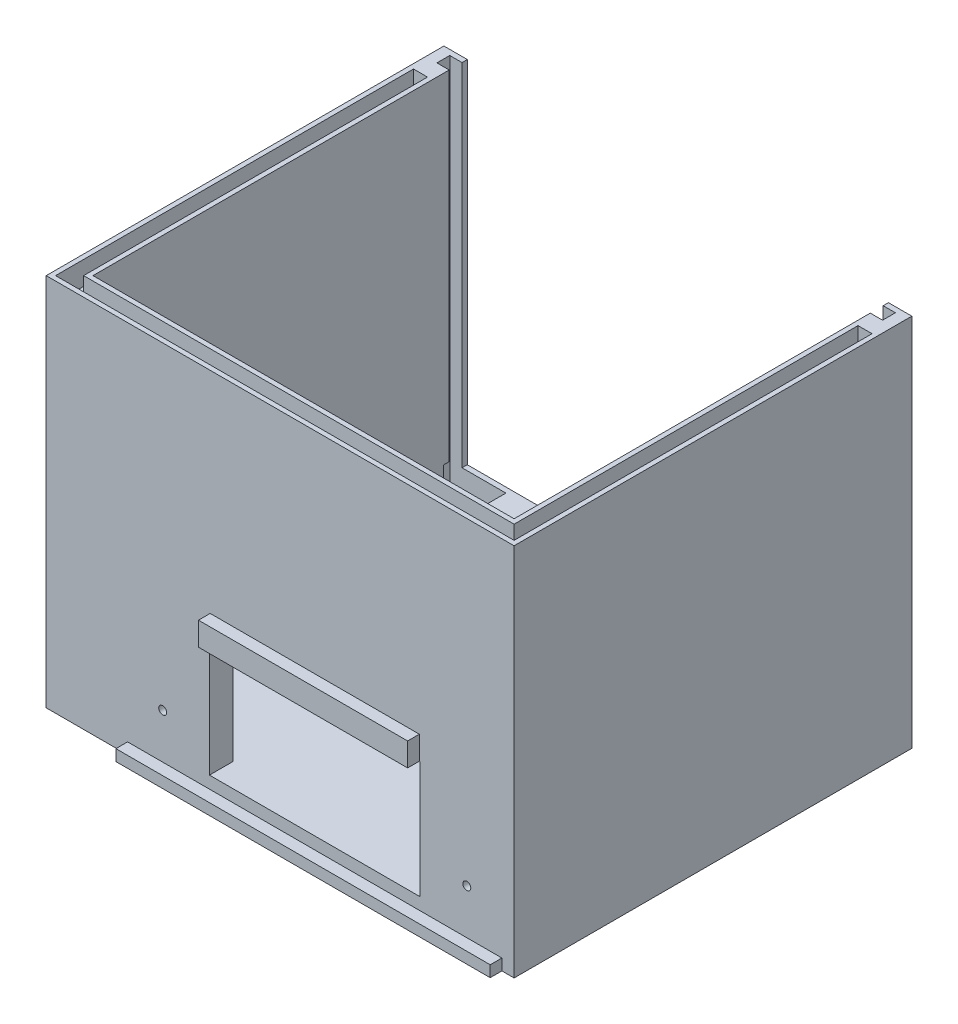
SolidWorks part; units mm, degrees
ref_plane "Front Plane" through (0, 0, 0) normal (0, 0, 1) x (1, 0, 0)
ref_plane "Top Plane" through (0, 0, 0) normal (0, 1, 0) x (1, 0, 0)
ref_plane "Right Plane" through (0, 0, 0) normal (1, 0, 0) x (0, 0, -1)
sketch "Croquis1" plane through (0, 0, 0) normal (0, 1, 0) x (1, 0, 0)
  line L1 (-100, -85) -> (100, -85)
  line L2 (-100, -85) -> (-100, 85)
  line L3 (-100, 85) -> (100, 85)
  line L4 (100, -85) -> (100, 85)
  line L5 (-100, -85) -> (100, 85) construction
  line L6 (-100, 85) -> (100, -85) construction
  point P0 (0, 0)
  dimension "D1" = 200
  dimension "D2" = 170
extrude "Saliente-Extruir1" add sketch "Croquis1" along normal blind 10
sketch "Croquis2" plane through (0, 10, 0) normal (0, 1, 0) x (1, 0, 0)
  line L0 (-100, 85) -> (-100, -85) construction
  line L1 (-100, -85) -> (-90, -85)
  line L2 (-100, -85) -> (-100, 85)
  line L3 (-100, 85) -> (-90, 85)
  line L4 (-90, -85) -> (-90, 85)
  line L5 (-100, -85) -> (-90, 85) construction
  line L6 (-100, 85) -> (-90, -85) construction
  line L7 (0, 0) -> (0, 38.7105) construction
  line L8 (100, 85) -> (90, -85) construction
  line L9 (100, -85) -> (90, 85) construction
  line L10 (90, -85) -> (90, 85)
  line L11 (100, 85) -> (90, 85)
  line L12 (100, -85) -> (100, 85)
  line L13 (100, -85) -> (90, -85)
  line L14 (-90, 85) -> (90, 85)
  line L15 (-90, 75) -> (90, 75)
  line L16 (-90, -75) -> (-30.21, -75)
  line L17 (-30.21, -75) -> (-30.21, -85)
  line L18 (-100, -85) -> (100, -85) construction
  line L19 (-30.21, -85) -> (-90, -85)
  line L20 (59.79, -85) -> (59.79, -75)
  line L21 (59.79, -75) -> (90, -75)
  line L22 (59.79, -85) -> (90, -85)
  point P0 (-95, 0)
  point P14 (95, 0)
  line M14 (100, -85) -> (100, 85)
  line M15 (100, 85) -> (-100, 85)
  line M16 (-100, 85) -> (-100, -85)
  line M17 (-100, -85) -> (100, -85)
  dimension "D1" = 10
  dimension "D2" = 10
  dimension "D3" = 10
  dimension "D4" = 69.79
  dimension "D5" = 40.21
  dimension "D6" = 10
extrude "Saliente-Extruir2" add sketch "Croquis2" along normal blind 150 contours L4 M17 M15 M16 | L10 M17 M14 M15 | L17 L16 L4 M17 | L21 L20 L10 M17 region at (-95, 10, 0) region at (-60.105, 10, 80) region at (74.895, 10, 80) region at (95, 10, 0)
sketch "Croquis3" plane through (0, 160, 0) normal (0, 1, 0) x (1, 0, 0)
  line L0 (-30.21, -75) -> (59.79, -75)
  line L1 (59.79, -75) -> (59.79, -85)
  line L2 (59.79, -85) -> (-30.21, -85)
  line L3 (-30.21, -85) -> (-30.21, -75)
extrude "Saliente-Extruir3" add sketch "Croquis3" against normal blind 100
sketch "Croquis4" plane through (0, 10, 65) normal (0, 1, 0) x (-1, 0, 0)
  line L1 (95.25, -147.75) -> (84.75, -147.75)
  line L2 (95.25, -147.75) -> (95.25, -142.25)
  line L3 (95.25, -142.25) -> (84.75, -142.25)
  line L4 (84.75, -147.75) -> (84.75, -142.25)
  line L5 (95.25, -147.75) -> (84.75, -142.25) construction
  line L6 (95.25, -142.25) -> (84.75, -147.75) construction
  line L8 (90, -142.25) -> (90, -147.75)
  line L9 (0, -65) -> (0, 148.7254) construction
  line L10 (-95.25, -142.25) -> (-84.75, -147.75) construction
  line L11 (-95.25, -147.75) -> (-84.75, -142.25) construction
  line L12 (-90, -142.25) -> (-90, -147.75)
  line L13 (-84.75, -147.75) -> (-84.75, -142.25)
  line L14 (-95.25, -142.25) -> (-84.75, -142.25)
  line L15 (-95.25, -147.75) -> (-95.25, -142.25)
  line L16 (-95.25, -147.75) -> (-84.75, -147.75)
  line L17 (-90, -150) -> (90, -150) construction
  line L18 (90, 10) -> (90, -150) construction
  point P0 (90, -145)
  point P20 (-90, -145)
  dimension "D1" = 5.5
  dimension "D2" = 5
  dimension "D3" = 10.5
extrude "Cortar-Extruir1" cut sketch "Croquis4" along normal blind 170 contours L2 L3 L1 | L15 L16 L14 region at (-92.625, 10, -80) region at (92.625, 10, -80)
sketch "Croquis7" plane through (0, 0, 85) normal (0, 0, 1) x (1, 0, 0)
  line L0 (-30.21, 60) -> (-30.21, 70)
  line L1 (-30.21, 70) -> (59.79, 70)
  line L2 (59.79, 70) -> (59.79, 60)
  line L3 (-30.21, 60) -> (59.79, 60)
  dimension "D1" = 10
extrude "Saliente-Extruir4" add sketch "Croquis7" along normal blind 5
sketch "Croquis8" plane through (0, 160, 0) normal (0, 1, 0) x (1, 0, 0)
  line L4 (98, 70) -> (98, -83)
  line L5 (98, -83) -> (-98, -83)
  line L6 (-98, -83) -> (-98, 70)
  line L8 (-98, 70) -> (-92, 70)
  line L9 (-92, 70) -> (-92, -77)
  line L10 (-92, -77) -> (92, -77)
  line L11 (92, -77) -> (92, 70)
  line L12 (92, 70) -> (98, 70)
  line L13 (100, -85) -> (100, 85) construction
  line L14 (90, -75) -> (90, 77.25) construction
  line L25 (-100, -85) -> (100, -85) construction
  line L26 (-90, -75) -> (90, -75) construction
  line L33 (-90, -75) -> (-90, 77.25) construction
  line L34 (-100, 85) -> (-100, -85) construction
  line L68 (-90, 85) -> (-100, 85) construction
  line L69 (100, 85) -> (90, 85) construction
  dimension "D1" = 2
  dimension "D2" = 2
  dimension "D3" = 2
  dimension "D4" = 2
  dimension "D5" = 2
  dimension "D7" = 15
  dimension "D8" = 15
  dimension "D6" = 2
extrude "Cortar-Extruir3" cut sketch "Croquis8" against normal blind 10 contours L8 region at (95.5135, 160, 6.5)
sketch "Croquis9" plane through (0, 10, 0) normal (0, 1, 0) x (1, 0, 0)
  line L0 (-95.25, 77.25) -> (-95.25, 82.75)
  line L1 (-95.25, 82.75) -> (-71.25, 82.75)
  line L2 (-71.25, 82.75) -> (-71.25, 77.25)
  line L4 (-71.25, 77.25) -> (-71.25, 74.75)
  line L5 (-71.25, 74.75) -> (-95.25, 74.75)
  line L6 (-95.25, 74.75) -> (-95.25, 77.25)
  dimension "D1" = 24
  dimension "D2" = 2.5
  dimension "D3" = 2.5
extrude "Cortar-Extruir4" cut sketch "Croquis9" against normal blind 30
extrude "Cortar-Extruir5" cut sketch "Croquis9<2>" along normal blind 5
sketch "Croquis9<2>" plane through (0, 10, 0) normal (0, 1, 0) x (1, 0, 0) same geometry as "Croquis9"
sketch "Croquis10" plane through (0, 0, 0) normal (0, -1, 0) x (1, 0, 0)
  line L0 (-71.25, -82.75) -> (-95.25, -82.75)
  line L1 (-95.25, -82.75) -> (-95.25, -74.75)
  line L2 (-95.25, -74.75) -> (-71.25, -74.75)
  line L3 (-71.25, -74.75) -> (-71.25, -82.75)
  line L4 (-68.25, -85.25) -> (-98.25, -85.25)
  line L5 (-98.25, -85.25) -> (-98.25, -71.75)
  line L6 (-98.25, -71.75) -> (-68.25, -71.75)
  line L7 (-68.25, -71.75) -> (-68.25, -85.25)
  dimension "D1" = 3
  dimension "D2" = 3
  dimension "D3" = 3
  dimension "D4" = 2.5
extrude "Saliente-Extruir5" add sketch "Croquis10" along normal blind 4.3
sketch "Croquis11" plane through (0, 0, -71.75) normal (0, 0, 1) x (1, 0, 0)
  line L0 (-68.25, -4.3) -> (-68.25, 0) construction
  line L1 (-68.25, 0) -> (-98.25, 0) construction
  circle A0 centre (-77.55, -2.1) radius 1.1
  circle A1 centre (-86.93, -2.1) radius 1.1
  dimension "D1" = 2.2
  dimension "D2" = 2.2
  dimension "D3" = 9.3
  dimension "D4" = 9.38
  dimension "D5" = 2.1
  dimension "D6" = 2.1
extrude "Cortar-Extruir6" cut sketch "Croquis11" against normal blind 14.3
sketch "Croquis12" plane through (0, 0, 0) normal (0, -1, 0) x (1, 0, 0)
  line L0 (-100, -85) -> (-100, 85) construction
  line L1 (0, 0) -> (-59.6706, 0) construction
  line L2 (100, -85) -> (-68.25, -85) construction
  circle A0 centre (-91.5, -55) radius 1.75
  circle A1 centre (18.5, -55) radius 1.75
  circle A2 centre (-91.5, 55) radius 1.75
  circle A3 centre (18.5, 55) radius 1.75
  dimension "D1" = 3.5
  dimension "D4" = 3.5
  dimension "D5" = 30
  dimension "D6" = 30
  dimension "D2" = 8.5
  dimension "D3" = 118.5
extrude "Cortar-Extruir7" cut sketch "Croquis12" against normal blind 6.4
sketch "Croquis13" plane through (0, 0, 85) normal (0, 0, 1) x (1, 0, 0)
  line L1 (-30.21, 10) -> (59.79, 10) construction
  line L2 (-30.21, 60) -> (-30.21, 10) construction
  line L3 (14.79, 10) -> (14.79, 41.54) construction
  circle A0 centre (-50.21, 24) radius 1.7
  circle A1 centre (79.79, 24) radius 1.7
  dimension "D3" = 3.4
  dimension "D1" = 14
  dimension "D2" = 20
extrude "Cortar-Extruir8" cut sketch "Croquis13" against normal blind 5
sketch "Croquis14" plane through (0, 0, 90) normal (0, 0, 1) x (1, 0, 0)
  line L0 (-30.21, 70) -> (-30.21, 60)
  line L1 (-30.21, 60) -> (-29.91, 60)
  line L2 (-30.21, 60) -> (59.79, 60) construction
  line L3 (-29.91, 60) -> (-29.91, 70)
  line L4 (59.79, 70) -> (-30.21, 70) construction
  line L5 (-29.91, 70) -> (-30.21, 70)
  line L6 (59.79, 70) -> (59.49, 70)
  line L7 (59.49, 70) -> (59.49, 60)
  line L8 (59.49, 60) -> (59.79, 60)
  line L9 (59.79, 60) -> (59.79, 70) construction
  line L10 (59.79, 60) -> (59.79, 70)
  dimension "D1" = 0.3
  dimension "D2" = 0.3
extrude "Cortar-Extruir9" cut sketch "Croquis14" against normal blind 5
sketch "Croquis15" plane through (0, 0, 85) normal (0, 0, 1) x (1, 0, 0)
  line L0 (14.79, 0) -> (94.79, 0)
  line L1 (-100, 0) -> (100, 0) construction
  line L2 (94.79, 0) -> (94.79, 4.8)
  line L3 (94.79, 4.8) -> (14.79, 4.8)
  line L4 (14.79, 4.8) -> (-65.21, 4.8)
  line L5 (-65.21, 4.8) -> (-65.21, 0)
  line L6 (-65.21, 0) -> (14.79, 0)
  line L7 (-30.21, 10) -> (59.79, 10) construction
  point P10 (14.79, 10)
  dimension "D1" = 80
  dimension "D2" = 4.8
  dimension "D3" = 80
extrude "Saliente-Extruir6" add sketch "Croquis15" along normal blind 5
